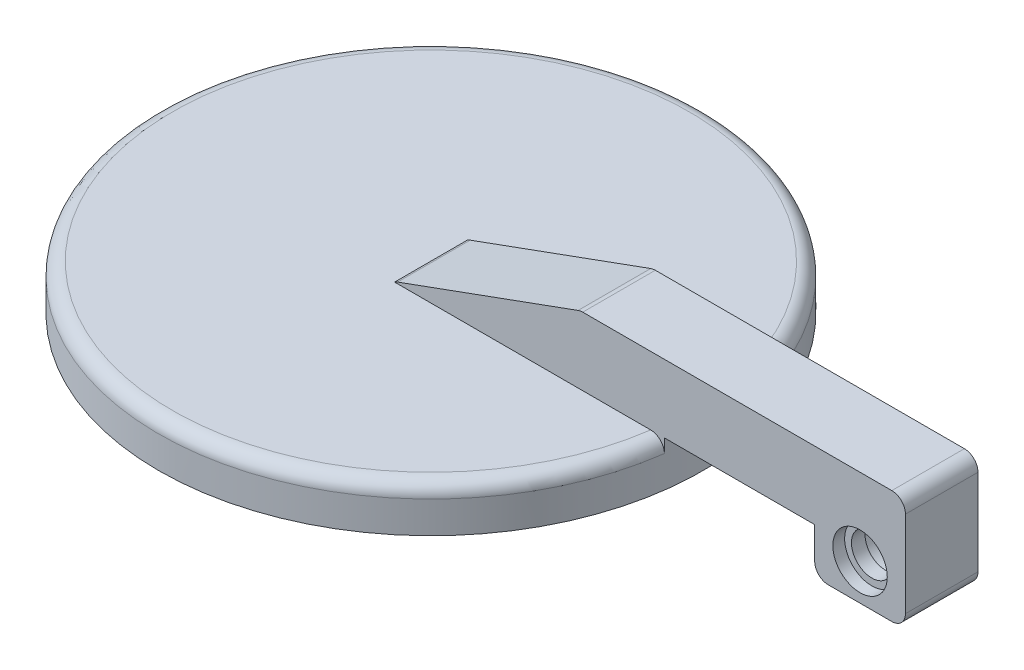
SolidWorks part; units mm, degrees
ref_plane "Front Plane" through (0, 0, 0) normal (0, 0, 1) x (1, 0, 0)
ref_plane "Top Plane" through (0, 0, 0) normal (0, 1, 0) x (1, 0, 0)
ref_plane "Right Plane" through (0, 0, 0) normal (1, 0, 0) x (0, 0, -1)
sketch "Sketch2" plane through (0, 0, 0) normal (0, 0, 1) x (1, 0, 0)
  line L7 (0, 0) -> (30, 0)
  line L8 (0, 0) -> (0, 5)
  line L9 (0, 5) -> (30, 5)
  line L10 (30, 0) -> (30, 5)
  dimension "D1" = 5
  dimension "D2" = 30
revolve "Revolve1" add sketch "Sketch2" angle 360 about L8
sketch "Sketch3" plane through (0, 5, 0) normal (0, 1, 0) x (1, 0, 0)
  line L0 (0, -10) -> (0, 10) construction
  line L1 (0, 10) -> (35, 10)
  line L2 (35, 10) -> (35, 6)
  line L3 (35, 6) -> (0, 6)
  line L4 (0, 10) -> (0, 6)
  line L5 (0, -10) -> (35, -10)
  line L6 (35, -10) -> (35, -6)
  line L7 (35, -6) -> (0, -6)
  line L8 (0, -6) -> (0, -10)
  line L9 (0, 4) -> (0, -4)
  line L10 (0, 4) -> (56.3, 4)
  line L11 (0, -4) -> (56.3, -4)
  line L12 (56.3, -4) -> (56.3, 4)
  point P4 (0, 0)
  point P13 (0, 0)
  circle M1 centre (0, 0) radius 30
  dimension "D1" = 20
  dimension "D2" = 35
  dimension "D3" = 4
  dimension "0.7" = 8
  dimension "D5" = 56.3
extrude "Boss-Extrude1" add sketch "Sketch3" along normal blind 7.5 contours L9 L11 L10 M1 | L11 L12 L10 M1 region at (14.9555, 5, 0) region at (43.1053, 5, 0)
sketch "Sketch4" plane through (0, 0, 0) normal (0, 0, 1) x (1, 0, 0)
  line L5 (35, 8.75) -> (37.8, 8.75) construction
  line L7 (56.3, 8.75) -> (37.8, 8.75) construction
  line L8 (56.3, 12.5) -> (56.3, 5) construction
  line L10 (-0.1339, 5) -> (20.4721, 12.5)
  line L11 (29.7321, 5) -> (-30, 5) construction
  line L12 (0, 12.5) -> (56.3, 12.5) construction
  line L13 (0, 5) -> (29.7321, 5) construction
  line L14 (20.4721, 12.5) -> (0, 12.5)
  line L15 (0, 12.5) -> (-0.1339, 5)
  circle A0 centre (37.8, 8.75) radius 2
  dimension "D3" = 4
  dimension "D1" = 20
  dimension "D2" = 18.5
extrude "Cut-Extrude1" cut sketch "Sketch4" against normal mid plane 30 contours L14 L15 L10
sketch "Sketch6" plane through (0, 5, 0) normal (0, -1, 0) x (1, 0, 0)
  line L6 (56.3, 4) -> (46.3, 4)
  line L7 (56.3, 4) -> (56.3, -4) construction
  line L8 (29.7321, 4) -> (56.3, 4) construction
  line L9 (46.3, 4) -> (46.3, -4)
  line L10 (29.7321, -4) -> (56.3, -4) construction
  line L11 (46.3, -4) -> (56.3, -4)
  line L12 (56.3, -4) -> (56.3, 4)
  dimension "D1" = 10
extrude "Boss-Extrude2" add sketch "Sketch6" along normal blind 5
sketch "Sketch7" plane through (0, 0, 4) normal (0, 0, 1) x (1, 0, 0)
  line L0 (51.3, 4) -> (51.3, 0) construction
  line L2 (56.3, 0) -> (46.3, 0) construction
  circle A0 centre (51.3, 4) radius 3
  dimension "D2" = 6
  dimension "D1" = 4
extrude "Cut-Extrude2" cut sketch "Sketch7" against normal blind 10
fillet "Fillet2" radius 1.5 6 edges at (46.3, 0, 0) (56.3, 0, 0) (56.3, 12.5, 0) (20.4721, 12.5, 0) (0, 5.0487, 0) (-30, 5, 0)
sketch "Sketch9" plane through (0, 0, -4) normal (0, 0, -1) x (-1, 0, 0)
  circle A0 centre (-51.3, 4) radius 3
  circle A1 centre (-51.3, 4) radius 4
  dimension "D1" = 6
  dimension "D2" = 8
sketch "Sketch10" plane through (0, 0, 4) normal (0, 0, 1) x (1, 0, 0)
  circle A0 centre (51.3, 4) radius 3
  circle A1 centre (51.3, 4) radius 2.25
  dimension "D1" = 6
  dimension "D2" = 4.5
extrude "Boss-Extrude4" add sketch "Sketch10" along normal blind 1.5 from offset 2.8 offset against normal yes
sketch "Sketch11" plane through (0, 0, 1.2) normal (0, 0, -1) x (-1, 0, 0)
  circle A0 centre (-51.3, 4) radius 2.6
  circle A1 centre (-51.3, 4) radius 3
  dimension "D1" = 5.2
extrude "Boss-Extrude5" add sketch "Sketch11" along normal blind 5.2
sketch "Sketch12" plane through (0, 0, 0) normal (0, -1, 0) x (1, 0, 0)
  line L0 (0, 30) -> (0, 25.5) construction
  circle A0 centre (0, 0) radius 30 construction
  circle A1 centre (0, 27.75) radius 1.5
  circle A2 centre (19.6222, 19.6222) radius 1.5
  circle A3 centre (27.75, 0) radius 1.5
  circle A4 centre (19.6222, -19.6222) radius 1.5
  circle A5 centre (0, -27.75) radius 1.5
  circle A6 centre (-19.6222, -19.6222) radius 1.5
  circle A7 centre (-27.75, 0) radius 1.5
  circle A8 centre (-19.6222, 19.6222) radius 1.5
  point P24 (0, 0)
  dimension "D2" = 3
  dimension "D1" = 4.5
  dimension "D3" = 8
extrude "Cut-Extrude3" cut sketch "Sketch12" against normal blind 0.5
